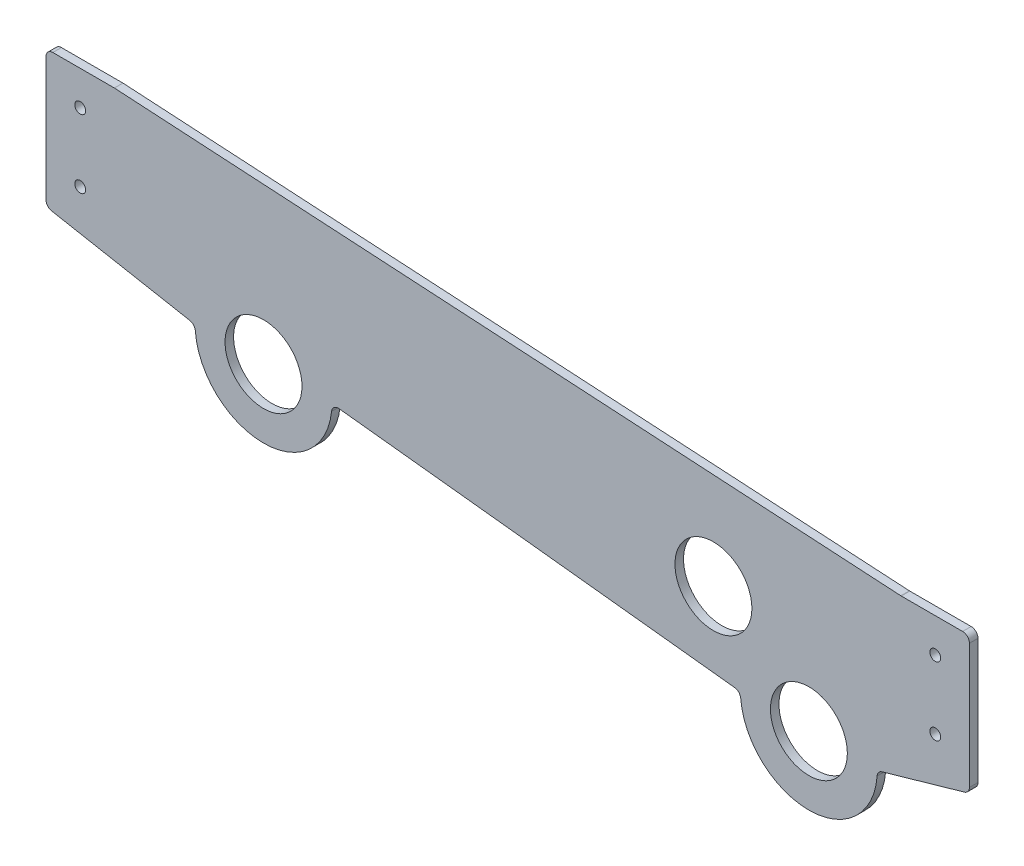
SolidWorks part; units mm, degrees
ref_plane "Front Plane" through (0, 0, 0) normal (0, 0, 1) x (1, 0, 0)
ref_plane "Top Plane" through (0, 0, 0) normal (0, 1, 0) x (1, 0, 0)
ref_plane "Right Plane" through (0, 0, 0) normal (1, 0, 0) x (0, 0, -1)
sketch "Sketch1" plane through (0, 0, 0) normal (0, 0, 1) x (1, 0, 0)
  line L0 (-101.6, -38.1991) -> (158.75, -38.1991) construction
  line L1 (-101.6, 76.1009) -> (273.6285, 76.1009) construction
  line L2 (-101.6, 164.2389) -> (101.6, 164.2389) construction
  line L3 (0, -88.9) -> (0, 235.6129) construction
  line L6 (-146.05, 113.4389) -> (-171.45, 113.4389) construction
  line L7 (-146.05, 113.4389) -> (-146.05, 164.2389) construction
  line L8 (-146.05, 164.2389) -> (-171.45, 164.2389)
  line L9 (-171.45, 113.4389) -> (-171.45, 164.2389)
  line L10 (-146.05, 113.4389) -> (-171.45, 164.2389) construction
  line L11 (-146.05, 164.2389) -> (-171.45, 113.4389) construction
  line L12 (-146.05, 164.2389) -> (146.05, 146.9669)
  line L17 (146.05, 96.1669) -> (171.45, 96.1669) construction
  line L18 (146.05, 96.1669) -> (146.05, 146.9669) construction
  line L19 (146.05, 146.9669) -> (171.45, 146.9669)
  line L20 (171.45, 96.1669) -> (171.45, 146.9669)
  line L21 (146.05, 96.1669) -> (171.45, 146.9669) construction
  line L22 (146.05, 146.9669) -> (171.45, 96.1669) construction
  line L23 (-146.05, 164.2389) -> (146.05, 146.9669)
  line L24 (-171.45, 113.4389) -> (-116.0814, 103.1319)
  line L25 (-65.2814, 103.1319) -> (86.4249, 86.356)
  line L26 (137.2249, 86.356) -> (171.45, 96.1669)
  circle A3 centre (0, 0) radius 88.9 construction
  circle A4 centre (111.8249, 86.356) radius 52.3875 construction
  circle A5 centre (-90.6814, 103.1319) radius 25.4 construction
  circle A6 centre (0, 172.7119) radius 88.9 construction
  circle A7 centre (-90.6814, 103.1319) radius 14.2875
  circle A8 centre (111.8249, 86.356) radius 14.2875
  circle A11 centre (-158.75, 151.5389) radius 2.0193
  circle A12 centre (158.75, 134.2669) radius 2.0193
  circle A13 centre (-90.6814, 103.1319) radius 23.495 construction
  circle A14 centre (111.8249, 86.356) radius 23.495 construction
  circle A15 centre (158.75, 108.8669) radius 2.0193
  circle A16 centre (-158.75, 126.1389) radius 2.0193
  arc A17 (-116.0814, 103.1319) -> (-65.2814, 103.1319) centre (-90.6814, 103.1319) ccw
  arc A18 (86.4249, 86.356) -> (137.2249, 86.356) centre (111.8249, 86.356) ccw
  point P12 (0, 164.2389)
  point P24 (-158.75, 151.5389)
  point P25 (158.75, 134.2669)
  point P37 (158.75, 121.5669)
  point P38 (5.3981, 114.787)
  point P39 (158.75, 121.5669)
  point P46 (158.75, 146.9669)
  point P48 (-158.75, 138.8389)
  dimension "D1" = 177.8
  dimension "D2" = 104.775
  dimension "D3" = 38.1991
  dimension "D5" = 50.8
  dimension "D10" = 177.8
  dimension "D12" = 28.575
  dimension "D13" = 28.575
  dimension "D14" = 4.0386
  dimension "D18" = 4.0386
  dimension "D19" = 46.99
  dimension "D20" = 46.99
  dimension "D32" = 25.4
  dimension "D33" = 25.4
  dimension "D4" = 114.3
  dimension "D6" = 203.2
  dimension "D7" = 158.75
  dimension "D8" = 203.2
  dimension "D9" = 202.438
  dimension "D11" = 260.35
  dimension "D15" = 189.738
  dimension "D16" = 317.5
  dimension "D17" = 172.466
  dimension "D22" = 12.7
  dimension "D23" = 25.4
  dimension "D24" = 12.7
  dimension "D25" = 12.7
  dimension "D26" = 25.4
  dimension "D27" = 71.374
  dimension "D28" = 50.8
  dimension "D29" = 50.8
  dimension "D30" = 12.7
  dimension "D31" = 61.107
  dimension "D21" = 2
extrude "Boss-Extrude1" add sketch "Sketch1" along normal blind 3.175 contours L20 L19 L12 L8 L9 A16 A15 A12 A11 A8 A7 region at (2.9498, 123.6895, 0)
fillet "Fillet1" radius 2.54 9 edges at (-171.45, 164.2389, 1.5875) (171.45, 146.9669, 1.5875) (171.45, 96.1669, 1.5875) (-171.45, 113.4389, 1.5875) (146.05, 146.9669, 1.5875) (86.4249, 86.356, 1.5875) (137.2249, 86.356, 1.5875) (-65.2814, 103.1319, 1.5875) (-116.0814, 103.1319, 1.5875)
sketch "Sketch2" plane through (0, 0, 3.175) normal (0, 0, 1) x (1, 0, 0)
  circle A0 centre (76.3807, 115.2355) radius 14.2875
  circle A2 centre (111.8249, 86.356) radius 14.2875 construction
  circle A3 centre (-90.6814, 103.1319) radius 14.2875 construction
  dimension "D1" = 28.575
  dimension "D2" = 45.72
  dimension "D3" = 167.5
extrude "Cut-Extrude1" cut sketch "Sketch2" against normal through all
